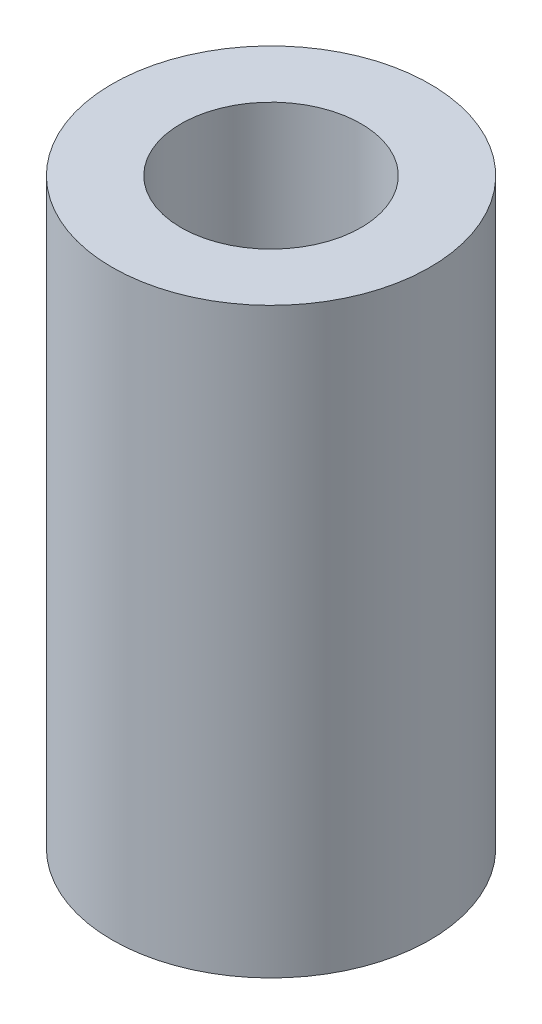
SolidWorks part; units mm, degrees
ref_plane "Front Plane" through (0, 0, 0) normal (0, 0, 1) x (1, 0, 0)
ref_plane "Top Plane" through (0, 0, 0) normal (0, 1, 0) x (1, 0, 0)
ref_plane "Right Plane" through (0, 0, 0) normal (1, 0, 0) x (0, 0, -1)
sketch "Sketch2" plane through (0, 0, 0) normal (0, 1, 0) x (1, 0, 0)
  circle A0 centre (0, 0) radius 3
  dimension "D1" = 6
extrude "Boss-Extrude1" add sketch "Sketch2" along normal mid plane 11
hole_wizard "M3 Clearance Hole1" positions "Sketch3" profile "Sketch4" hole size "M3" standard "ANSI Metric" end condition through all
sketch "Sketch3" plane through (0, 5.5, 0) normal (0, 1, 0) x (1, 0, 0)
  point P0 (0, 0)
sketch "Sketch4" plane through (0, 5.5, 0) normal (1, 0, 0) x (0, 0, 1)
  line L0 (0, 0) -> (0, 11)
  line L1 (0, 11) -> (1.7, 11)
  line L2 (1.7, 11) -> (1.7, 0)
  line L5 (1.7, 0) -> (0, 0)
  line L11 (0, -6.35) -> (0, 107.95) construction
  dimension "Thru Hole Dia." = 3.4
  dimension "Thru Hole Depth" = 11
